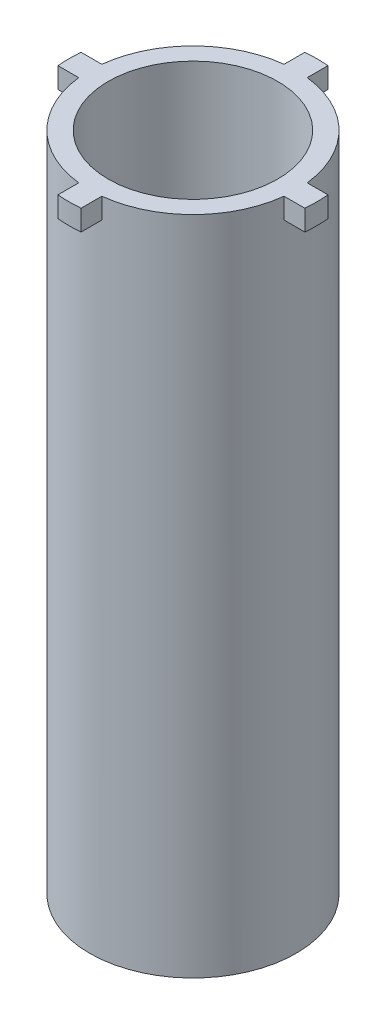
SolidWorks part; units mm, degrees
ref_plane "Front Plane" through (0, 0, 0) normal (0, 0, 1) x (1, 0, 0)
ref_plane "Top Plane" through (0, 0, 0) normal (0, 1, 0) x (1, 0, 0)
ref_plane "Right Plane" through (0, 0, 0) normal (1, 0, 0) x (0, 0, -1)
sketch "Sketch1" plane through (0, 0, 0) normal (0, 1, 0) x (1, 0, 0)
  line L0 (1.4, 12.4214) -> (1.4, 14.9345)
  line L2 (-1.4, -14.9345) -> (-1.4, -12.4214)
  line L4 (1.4, -14.9345) -> (1.4, -12.4214)
  line L5 (-1.0887, -14.9604) -> (-0.9073, -12.467) construction
  line L6 (-1.0887, 14.9604) -> (-0.9073, 12.467) construction
  line L7 (-14.9345, 1.4) -> (-12.4214, 1.4)
  line L9 (-14.9345, -1.4) -> (-12.4214, -1.4)
  line L11 (-14.9594, 1.1024) -> (-12.4662, 0.9187) construction
  line L12 (-14.9594, -1.1024) -> (-12.4662, -0.9187) construction
  line L13 (0.9073, 12.467) -> (1.0887, 14.9604) construction
  line L15 (-1.4, 12.4214) -> (-1.4, 14.9345)
  line L16 (12.4214, 1.4) -> (14.9345, 1.4)
  line L17 (12.4662, 0.9187) -> (14.9594, 1.1024) construction
  line L18 (12.4662, -0.9187) -> (14.9594, -1.1024) construction
  line L19 (12.4214, -1.4) -> (14.9345, -1.4)
  line L21 (0.9073, -12.467) -> (1.0887, -14.9604) construction
  circle A0 centre (0, 0) radius 15
  circle A1 centre (0, 0) radius 12.5
  circle A2 centre (0, 0) radius 10.25
  dimension "D1" = 30
  dimension "D2" = 20.5
extrude "Boss-Extrude1" add sketch "Sketch1" against normal blind 2.5 contours A1 L0 A0 L15 | A1 L19 A0 L16 | A1 L7 A0 L9 | A1 L2 A0 L4 region at (0, 0, -13.726) region at (13.726, 0, 0) region at (-13.726, 0, 0) region at (0, 0, 13.726)
extrude "Boss-Extrude2" add sketch "Sketch1<3>" against normal blind 80 contours A1 A2 region at (8.5888, 0, -8.5888)
sketch "Sketch1<3>" plane through (0, 0, 0) normal (0, 1, 0) x (1, 0, 0) same geometry as "Sketch1"
